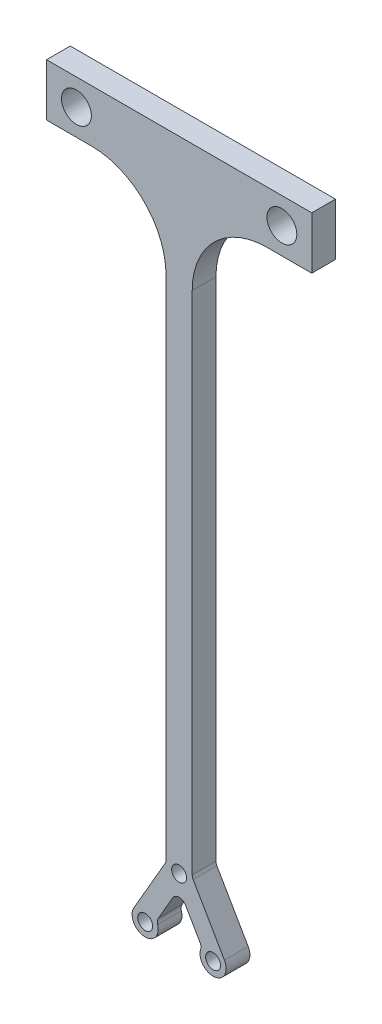
SolidWorks part; units mm, degrees
ref_plane "Front Plane" through (0, 0, 0) normal (0, 0, 1) x (1, 0, 0)
ref_plane "Top Plane" through (0, 0, 0) normal (0, 1, 0) x (1, 0, 0)
ref_plane "Right Plane" through (0, 0, 0) normal (1, 0, 0) x (0, 0, -1)
sketch "Sketch1" plane through (0, 0, 0) normal (0, 0, 1) x (1, 0, 0)
  line L0 (0, 0) -> (0, 5.25) construction
  line L1 (0, 0) -> (-9.0933, -5.25) construction
  line L2 (9.0933, -5.25) -> (0, 0) construction
  line L3 (0, 0) -> (9.5391, 0) construction
  line L4 (1.75, 90.7189) -> (17.75, 90.7189)
  line L7 (-1.884, 5.4869) -> (-6.0622, -1.75)
  line L8 (-1.75, 90.7189) -> (-17.75, 90.7189)
  line L9 (0, 5.25) -> (0, 3.25) construction
  line L10 (1.884, 5.4869) -> (6.0622, -1.75)
  line L17 (-2.783, -1.3203) -> (-0.866, 2)
  line L18 (0, 5.25) -> (-1.5155, 6.125) construction
  line L19 (-17.75, 90.7189) -> (-17.75, 83.7189)
  line L20 (-4.5466, -2.625) -> (-3.0311, -1.75) construction
  line L25 (-17.75, 83.7189) -> (-11.75, 83.7189)
  line L26 (0, 5.25) -> (1.5155, 6.125) construction
  line L27 (4.5466, -2.625) -> (3.0311, -1.75) construction
  line L28 (2.783, -1.3203) -> (0.866, 2)
  line L33 (11.75, 83.7189) -> (17.75, 83.7189)
  line L34 (1.75, 5.25) -> (-1.75, 5.25) construction
  line L36 (1.75, 5.9869) -> (1.75, 73.7189)
  line L37 (-1.75, 5.9869) -> (-1.75, 73.7189)
  line L38 (1.75, 90.7189) -> (-1.75, 90.7189)
  line L39 (17.75, 83.7189) -> (17.75, 90.7189)
  line L40 (-17.75, 87.2189) -> (17.75, 87.2189) construction
  circle A0 centre (0, 5.25) radius 1
  circle A14 centre (-4.5466, -2.625) radius 1
  circle A15 centre (4.5466, -2.625) radius 1
  arc A20 (-6.0622, -1.75) -> (-2.8732, -2.1129) centre (-4.5466, -2.625) ccw
  arc A21 (2.8732, -2.1129) -> (6.0622, -1.75) centre (4.5466, -2.625) ccw
  circle A22 centre (-13.75, 87.2189) radius 2
  circle A23 centre (13.75, 87.2189) radius 2
  arc A24 (-11.75, 83.7189) -> (-1.75, 73.7189) centre (-11.75, 73.7189) cw
  arc A25 (11.75, 83.7189) -> (1.75, 73.7189) centre (11.75, 73.7189) ccw
  arc A26 (0.866, 2) -> (-0.866, 2) centre (0, 1.5) ccw
  arc A27 (-2.8732, -2.1129) -> (-2.783, -1.3203) centre (-1.917, -1.8203) cw
  arc A28 (2.783, -1.3203) -> (2.8732, -2.1129) centre (1.917, -1.8203) cw
  arc A29 (-1.884, 5.4869) -> (-1.75, 5.9869) centre (-2.75, 5.9869) ccw
  arc A30 (1.884, 5.4869) -> (1.75, 5.9869) centre (2.75, 5.9869) cw
  point P39 (-1.75, 83.7189)
  point P44 (0, 3.5)
  point P53 (-1.75, 5.7189)
  dimension "D3" = 85
  dimension "D4" = 3.5
  dimension "D5" = 120
  dimension "D6" = 2
  dimension "D15" = 16
  dimension "D14" = 2
  dimension "D16" = 16
  dimension "D17" = 7
  dimension "D18" = 4
  dimension "D8" = 3.5
  dimension "D12" = 3.5
  dimension "D19" = 4
  dimension "D22" = 10
  dimension "D23" = 1
  dimension "D24" = 1
  dimension "D25" = 1
  dimension "D26" = 1
  dimension "D27" = 1
  dimension "D1" = 120
  dimension "D2" = 120
  dimension "D7" = 120
  dimension "D9" = 2.625
  dimension "D10" = 2.625
  dimension "D11" = 7.4689
  dimension "D13" = 60
  dimension "D20" = 4
  dimension "D21" = 4
extrude "Boss-Extrude1" add sketch "Sketch1" along normal blind 3.175
